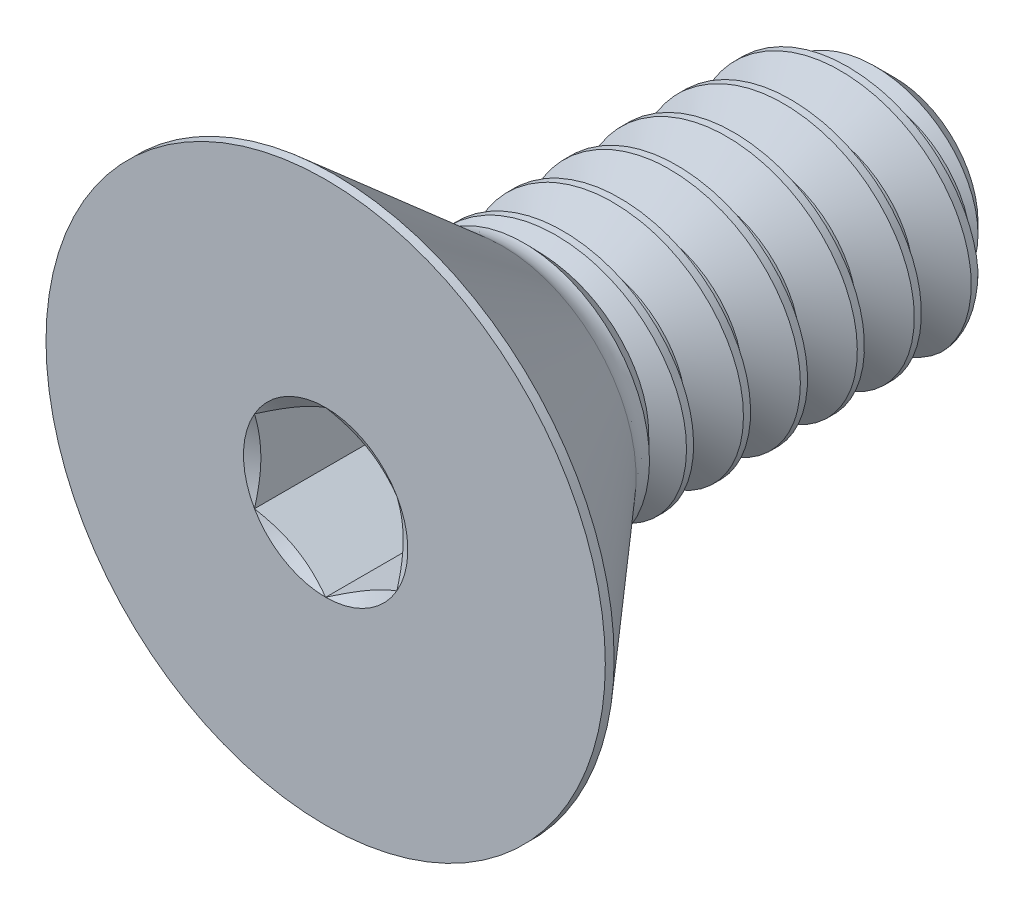
SolidWorks part; units mm, degrees
ref_plane "Front" through (0, 0, 0) normal (0, 0, 1) x (1, 0, 0)
ref_plane "Top" through (0, 0, 0) normal (0, 1, 0) x (1, 0, 0)
ref_plane "Right" through (0, 0, 0) normal (1, 0, 0) x (0, 0, -1)
sketch "Sketch1" plane through (0, 0, 0) normal (1, 0, 0) x (0, 0, -1)
  line L0 (0, 3.8989) -> (0.1232, 3.8989) construction
  line L1 (0.1232, 3.8989) -> (2.4638, 1.8642) construction
  line L2 (0, 1.7526) -> (7.9375, 1.7526)
  line L3 (7.9375, 1.7526) -> (7.9375, 0)
  line L4 (7.9375, 0) -> (0, 0)
  line L5 (0, 0) -> (0, 3.8989) construction
  line L6 (0, 3.8989) -> (0, -3.8989) construction
  line L7 (7.9375, 1.7526) -> (7.9375, -1.7526) construction
  line L8 (0, -3.8989) -> (0.1232, -3.8989) construction
  line L9 (0.1232, -3.8989) -> (2.4638, -1.8642) construction
  line L11 (0, 1.7526) -> (0, 0)
  line L12 (2.7624, 1.7526) -> (2.7624, 0) construction
  line L13 (-17.4625, 0) -> (-17.4625, 1.7526) construction
  arc A1 (2.4638, 1.8642) -> (2.7624, 1.7526) centre (2.7624, 2.2077) ccw construction
  dimension "D1" = 0.1232
  dimension "Min Thread" = 25.4
revolve "Revolve1" add sketch "Sketch1" angle 360 mid plane about L4
sketch "Sketch3" plane through (0, 0, -7.9375) normal (0, 0, -1) x (-1, 0, 0)
  circle A0 centre (0, 0) radius 1.7526
curve "Helix/Spiral1" pitch 0.7937 height 7.9375 radius 1.7526 centre (0, 0, -7.9375) axis (0, 0, 1) start towards (0, 1, 0)
sketch "Sketch2" plane through (0, 0, 0) normal (1, 0, 0) x (0, 0, -1)
  line L0 (7.9375, 1.7526) -> (8.632, 1.7526)
  line L1 (8.632, 1.7526) -> (8.3344, 1.237)
  line L2 (8.3344, 1.237) -> (8.2352, 1.237)
  line L3 (8.2352, 1.237) -> (7.9375, 1.7526)
  line L4 (8.0863, 1.4948) -> (8.4832, 1.4948) construction
  dimension "D1" = 60
  dimension "D2" = 0.0992
  dimension "D3" = 0.3969
ref_plane "Plane2" through (0, 0, 17.4625) normal (0, 0, 1) x (1, 0, 0)
chamfer "Chamfer1" distance 0.5953 angle 45 1 edges at (-1.7526, 0, -7.9375)
sweep "Cut-Sweep1" cut profiles "Sketch2" path "Helix/Spiral1" align with end faces yes
sketch "Sketch7" plane through (0, 0, 0) normal (1, 0, 0) x (0, 0, -1)
  line L0 (0, 3.8989) -> (0.1232, 3.8989) construction
  line L1 (0.1232, 3.8989) -> (2.4638, 1.8642) construction
  line L2 (0, 3.8989) -> (0.1232, 3.8989)
  line L3 (0.1232, 3.8989) -> (2.4638, 1.8642)
  line L4 (2.7624, 1.7526) -> (2.7624, 0) construction
  line L5 (2.7624, 1.7526) -> (2.7624, 0)
  line L7 (0, 0) -> (0, 3.8989) construction
  line L8 (0, 0) -> (0, 3.8989)
  line L9 (0, 0) -> (2.7624, 0)
  line L10 (5.7417, 0) -> (-5.7417, 0) construction
  arc A0 (2.4638, 1.8642) -> (2.7624, 1.7526) centre (2.7624, 2.2077) ccw construction
  arc A1 (2.4638, 1.8642) -> (2.7624, 1.7526) centre (2.7624, 2.2077) ccw
revolve "Revolve2" add sketch "Sketch7" angle 360 mid plane about L9
ref_plane "Plane1" through (0, 0, -2.7624) normal (0, 0, 1) x (1, 0, 0)
sketch "Sketch8" plane through (0, 0, -2.7624) normal (0, 0, 1) x (1, 0, 0)
  circle A0 centre (0, 0) radius 1.7526
extrude "Boss-Extrude1" add sketch "Sketch8" against normal through all draft 46
sketch "Sketch5" plane through (0, 0, 0) normal (0, 0, 1) x (1, 0, 0)
  line L0 (0, 0) -> (-1.1457, 0) construction
  line L1 (0, 0) -> (-2.7496, 1.5875) construction
  line L2 (0, 0) -> (-2.7496, -1.5875) construction
  line L6 (0, 1.1457) -> (0, 0.9449) construction
  line L7 (0, 0.9449) -> (0, 0.7441) construction
  line L9 (0, 1.1457) -> (-0.9922, 0.5728)
  line L10 (-0.9922, 0.5728) -> (-0.9922, -0.5728)
  line L11 (-0.9922, -0.5728) -> (0, -1.1457)
  line L12 (0, -1.1457) -> (0.9922, -0.5728)
  line L13 (0.9922, -0.5728) -> (0.9922, 0.5728)
  line L14 (0.9922, 0.5728) -> (0, 1.1457)
  circle A0 centre (0, 0) radius 1.1457 construction
  circle A1 centre (0, 0) radius 0.9449 construction
  circle A2 centre (0, 0) radius 0.7441 construction
  circle A3 centre (0, 0) radius 0.9922 construction
  dimension "D3" = 1.4883
  dimension "D4" = 30
  dimension "D5" = 30
  dimension "Hex" = 1.9844
extrude "Cut-Extrude2" cut sketch "Sketch5" against normal blind 1.7247
sketch "Sketch6" plane through (0, 0, 0) normal (0, 0, 1) x (1, 0, 0)
  circle A0 centre (0, 0) radius 1.1457
extrude "Cut-Extrude3" cut sketch "Sketch6" against normal blind 1.7247 draft 60
sketch "Sketch9" [suppressed] plane through (0, 0, -3.6076) normal (0, 0, 1) x (1, 0, 0)
  circle A1 centre (0, 0) radius 2.413
  circle A2 centre (0, 0) radius 2.413
  point P0 (0, 2.413)
  dimension "D1" = 0
extrude "Boss-Extrude2" [suppressed] add sketch "Sketch9" against normal up to surface (15.4424 mm away) up to plane "Plane2"
sketch "Sketch10" plane through (0, 0, 0) normal (1, 0, 0) x (0, 0, -1)
  line L0 (7.9375, 1.7526) -> (7.9375, -1.7526) construction
  point P0 (6.7469, -1.7526)
  dimension "D1" = 1.1906
equation "\"D3@Helix/Spiral1\" = \"Lg@Sketch1\""
equation "\"D2@Sketch2\" = \"D4@Helix/Spiral1\" * .125"
equation "\"D3@Sketch2\" = \"D4@Helix/Spiral1\" * .5"
equation "\"D1@Chamfer1\" = \"D4@Helix/Spiral1\" * .75"
equation "\"D1@Cut-Extrude2\" = \"Head Ht@Sketch1\" * .7"
equation "\"D1@Sketch1\" = \"Head Ht@Sketch1\" * .05"
equation "\"D1@Sketch10\" = \"D4@Helix/Spiral1\" * 1.5"
equation "\"D1@Cut-Extrude3\" = \"D1@Cut-Extrude2\""
equation "\"D3@Sketch5\" = \"Hex@Sketch5\" * .75"
